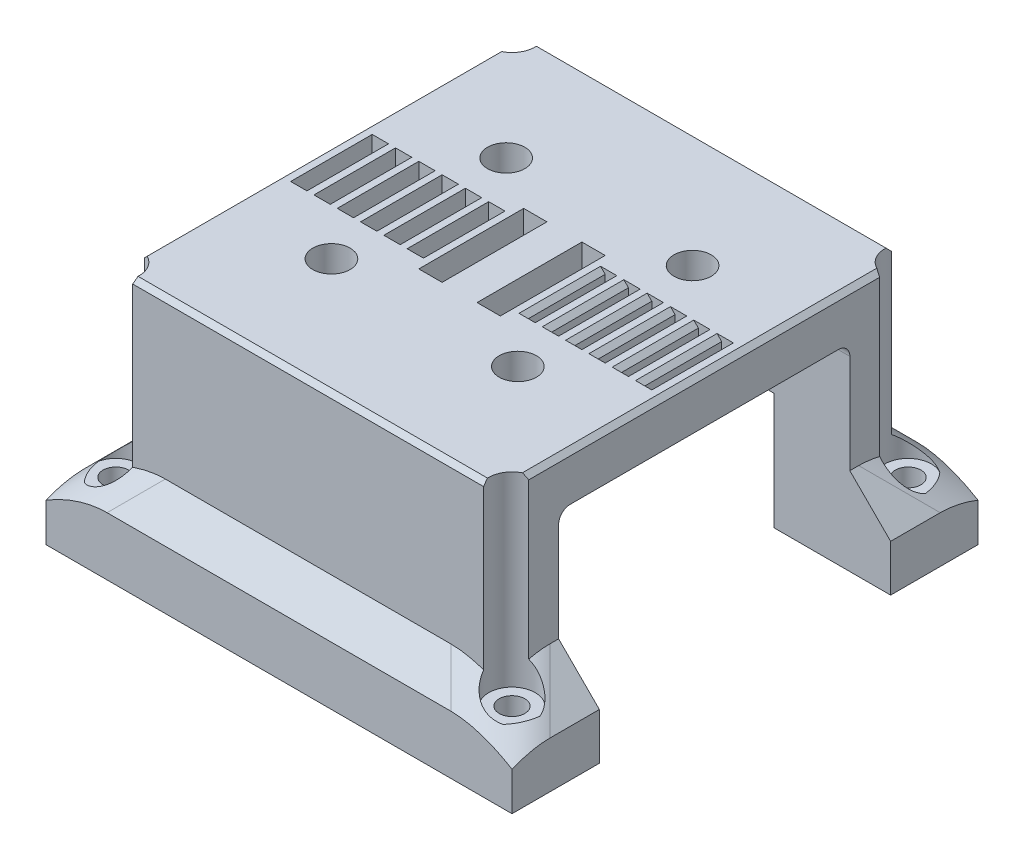
SolidWorks part; units mm, degrees
ref_plane "前视基准面" through (0, 0, 0) normal (0, 0, 1) x (1, 0, 0)
ref_plane "上视基准面" through (0, 0, 0) normal (0, 1, 0) x (1, 0, 0)
ref_plane "右视基准面" through (0, 0, 0) normal (1, 0, 0) x (0, 0, -1)
other "Configuration Table"
sketch "草图1" plane through (0, 0, 0) normal (0, 1, 0) x (1, 0, 0)
  line L1 (0, 0) -> (33, 0)
  line L2 (0, 0) -> (0, -35)
  line L3 (0, -35) -> (33, -35)
  line L4 (33, 0) -> (33, -35)
  circle A0 centre (8.5, -10) radius 1.6
  circle A1 centre (24.5, -10) radius 1.6
  circle A2 centre (24.5, -25) radius 1.6
  circle A3 centre (8.5, -25) radius 1.6
  dimension "D1" = 3.2
  dimension "D4" = 35
  dimension "D5" = 33
  dimension "D6" = 10
  dimension "D7" = 8.5
  dimension "D2" = 2
  dimension "D3" = 2
extrude "凸台-拉伸1" add sketch "草图1" along normal blind 4
sketch "草图2" plane through (0, 4, 0) normal (0, 1, 0) x (1, 0, 0)
  line L0 (0, 0) -> (0, -35) construction
  line L1 (1, -14) -> (2, -14)
  line L2 (1, -14) -> (1, -21)
  line L3 (1, -21) -> (2, -21)
  line L4 (2, -14) -> (2, -21)
  line L5 (3, -14) -> (3, -21)
  line L6 (3, -14) -> (4, -14)
  line L7 (4, -14) -> (4, -21)
  line L8 (3, -21) -> (4, -21)
  line L9 (5, -14) -> (5, -21)
  line L10 (5, -14) -> (6, -14)
  line L11 (6, -14) -> (6, -21)
  line L12 (5, -21) -> (6, -21)
  line L13 (7, -14) -> (7, -21)
  line L14 (7, -14) -> (8, -14)
  line L15 (8, -14) -> (8, -21)
  line L16 (7, -21) -> (8, -21)
  line L17 (9, -14) -> (9, -21)
  line L18 (9, -14) -> (10, -14)
  line L19 (10, -14) -> (10, -21)
  line L20 (9, -21) -> (10, -21)
  line L21 (11, -14) -> (11, -21)
  line L22 (11, -14) -> (12, -14)
  line L23 (12, -14) -> (12, -21)
  line L24 (11, -21) -> (12, -21)
  line L25 (13, -14) -> (13, -21)
  line L26 (13, -14) -> (14, -14)
  line L27 (14, -14) -> (14, -21)
  line L28 (13, -21) -> (14, -21)
  line L29 (15, -14) -> (15, -21)
  line L30 (15, -14) -> (16, -14)
  line L31 (16, -14) -> (16, -21)
  line L32 (15, -21) -> (16, -21)
  line L33 (17, -14) -> (17, -21)
  line L34 (17, -14) -> (18, -14)
  line L35 (18, -14) -> (18, -21)
  line L36 (17, -21) -> (18, -21)
  line L37 (19, -14) -> (19, -21)
  line L38 (19, -14) -> (20, -14)
  line L39 (20, -14) -> (20, -21)
  line L40 (19, -21) -> (20, -21)
  line L41 (21, -14) -> (21, -21)
  line L42 (21, -14) -> (22, -14)
  line L43 (22, -14) -> (22, -21)
  line L44 (21, -21) -> (22, -21)
  line L45 (23, -14) -> (23, -21)
  line L46 (23, -14) -> (24, -14)
  line L47 (24, -14) -> (24, -21)
  line L48 (23, -21) -> (24, -21)
  line L49 (25, -14) -> (25, -21)
  line L50 (25, -14) -> (26, -14)
  line L51 (26, -14) -> (26, -21)
  line L52 (25, -21) -> (26, -21)
  line L53 (27, -14) -> (27, -21)
  line L54 (27, -14) -> (28, -14)
  line L55 (28, -14) -> (28, -21)
  line L56 (27, -21) -> (28, -21)
  line L57 (29, -14) -> (29, -21)
  line L58 (29, -14) -> (30, -14)
  line L59 (30, -14) -> (30, -21)
  line L60 (29, -21) -> (30, -21)
  line L61 (31, -14) -> (31, -21)
  line L62 (31, -14) -> (32, -14)
  line L63 (32, -14) -> (32, -21)
  line L64 (31, -21) -> (32, -21)
  point P6 (1, -17.5)
  point P7 (0, -17.5)
  dimension "D1" = 1
  dimension "D2" = 1
  dimension "D3" = 7
  dimension "D4" = 0
  dimension "D5" = 16
extrude "切除-拉伸1" cut sketch "草图2" against normal blind 1.5
chamfer "倒角1" distance 0.4 angle 45 16 edges at (31, 4, 17.5) (29, 4, 17.5) (27, 4, 17.5) (25, 4, 17.5) (23, 4, 17.5) (21, 4, 17.5) (19, 4, 17.5) (17, 4, 17.5) (14, 4, 17.5) (12, 4, 17.5) (10, 4, 17.5) (6, 4, 17.5) (4, 4, 17.5) (2, 4, 17.5) (16, 4, 17.5) (8, 4, 17.5)
sketch "草图3" plane through (0, 4, 0) normal (0, 1, 0) x (1, 0, 0)
  line L0 (14, -14) -> (13, -14) construction
  line L1 (15, -13) -> (13, -13)
  line L2 (15, -13) -> (15, -22)
  line L3 (15, -22) -> (13, -22)
  line L4 (13, -13) -> (13, -22)
  line L5 (18, -13) -> (20, -13)
  line L6 (18, -13) -> (18, -22)
  line L7 (18, -22) -> (20, -22)
  line L8 (20, -13) -> (20, -22)
  line L9 (13, -21) -> (14, -21) construction
  line L10 (20, -14) -> (18.6, -14) construction
  line L11 (19, -21) -> (20, -21) construction
  dimension "D1" = 1
  dimension "D2" = 1
  dimension "D3" = 1
  dimension "D4" = 1
extrude "切除-拉伸2" cut sketch "草图3" against normal through all
sketch "草图4" plane through (0, 4, 0) normal (0, 1, 0) x (1, 0, 0)
  line L1 (15, -14) -> (18, -14)
  line L2 (15, -14) -> (15, -21)
  line L3 (15, -21) -> (18, -21)
  line L4 (18, -14) -> (18, -21)
extrude "凸台-拉伸2" add sketch "草图4" against normal blind 1.5
sketch "草图5" plane through (0, 0, 0) normal (0, -1, 0) x (-1, 0, 0)
  line L0 (-33, -35) -> (-33, 0) construction
  line L1 (0, -35) -> (-33, -35)
  line L2 (0, -35) -> (0, -30)
  line L3 (0, -30) -> (-33, -30)
  line L4 (-33, -35) -> (-33, -30)
  line L5 (0, 0) -> (0, -35) construction
  line L6 (-33, 0) -> (0, 0)
  line L7 (-33, 0) -> (-33, -5)
  line L8 (-33, -5) -> (0, -5)
  line L9 (0, 0) -> (0, -5)
  dimension "D1" = 5
  dimension "D2" = 5
extrude "凸台-拉伸3" add sketch "草图5" along normal blind 13
sketch "草图7" plane through (0, -13, 0) normal (0, -1, 0) x (-1, 0, 0)
  line L0 (-33, -35) -> (0, -35) construction
  line L1 (3.5, -37.5) -> (-36.5, -37.5)
  line L2 (3.5, -37.5) -> (3.5, -30)
  line L3 (3.5, -30) -> (-36.5, -30)
  line L4 (-36.5, -37.5) -> (-36.5, -30)
  line L5 (0, 0) -> (-33, 0) construction
  line L6 (-36.5, 2.5) -> (3.5, 2.5)
  line L7 (-36.5, 2.5) -> (-36.5, -5)
  line L8 (-36.5, -5) -> (3.5, -5)
  line L9 (3.5, 2.5) -> (3.5, -5)
  line L10 (-33, -5) -> (0, -5) construction
  line L11 (0, -30) -> (-33, -30) construction
  point P4 (-16.5, -37.5)
  point P7 (-16.5, -35)
  point P12 (-16.5, 2.5)
  point P15 (-16.5, 0)
  dimension "D1" = 40
  dimension "D2" = 0
  dimension "D3" = 40
  dimension "D4" = 0
  dimension "D5" = 7.5
  dimension "D6" = 7.5
  dimension "D7" = 0
  dimension "D8" = 0
extrude "凸台-拉伸4" add sketch "草图7" along normal blind 4
chamfer "倒角4" distance 3.5 angle 45 6 edges at (33, -13, 2.5) (16.5, -13, 0) (0, -13, 2.5) (33, -13, 32.5) (0, -13, 32.5) (16.5, -13, 35)
sketch "草图8" plane through (0, -17, 0) normal (0, -1, 0) x (-1, 0, 0)
  line L0 (-36.5, -37.5) -> (3.5, -37.5) construction
  line L1 (3.5, -37.5) -> (3.5, -30) construction
  circle A0 centre (0.5, -34.5) radius 1.1
  circle A1 centre (-33.5, -34.5) radius 1.1
  circle A2 centre (-33.5, -0.5) radius 1.1
  circle A3 centre (0.5, -0.5) radius 1.1
  dimension "D1" = 2.2
  dimension "D2" = 3
  dimension "D3" = 3
  dimension "D4" = 2
  dimension "D5" = 2
extrude "切除-拉伸3" cut sketch "草图8" against normal blind 10
fillet "圆角1" radius 1 2 edges at (16.5, 0, 30) (16.5, 0, 5)
sketch "草图9" plane through (0, -17, 0) normal (0, -1, 0) x (-1, 0, 0)
  line L0 (-36.5, -5) -> (3.5, -5) construction
  line L1 (-6.5, -5) -> (-26.5, -5)
  line L2 (-6.5, -5) -> (-6.5, 2.5)
  line L3 (-6.5, 2.5) -> (-26.5, 2.5)
  line L4 (-26.5, -5) -> (-26.5, 2.5)
  line L5 (3.5, 2.5) -> (-36.5, 2.5) construction
  line L6 (3.5, -5) -> (3.5, 2.5) construction
  line L7 (-36.5, 2.5) -> (-36.5, -5) construction
  dimension "D1" = 10
  dimension "D2" = 10
extrude "切除-拉伸4" cut sketch "草图9" against normal blind 10
sketch "草图10" plane through (0, 4, 0) normal (0, 1, 0) x (1, 0, 0)
  circle A0 centre (33.5, -0.5) radius 2
  circle A1 centre (33.5, -34.5) radius 2
  circle A2 centre (-0.5, -34.5) radius 2
  circle A3 centre (-0.5, -0.5) radius 2
  dimension "D1" = 4
  dimension "D2" = 4
  dimension "D3" = 4
  dimension "D4" = 4
extrude "切除-拉伸5" cut sketch "草图10" against normal blind 16
chamfer "倒角3" distance 0.4 angle 45 4 edges at (33, 4, 17.5) (16.5, 4, 35) (0, 4, 17.5) (16.5, 4, 0)
fillet "圆角2" radius 6 4 edges at (-1.9114, -11.4114, -1.9114) (-1.9114, -11.4114, 36.9114) (34.9114, -11.4114, 36.9114) (34.9114, -11.4114, -1.9114)
equation "\"D4@草图1\"=15+20"
equation "\"D5@草图1\"=16+17"
